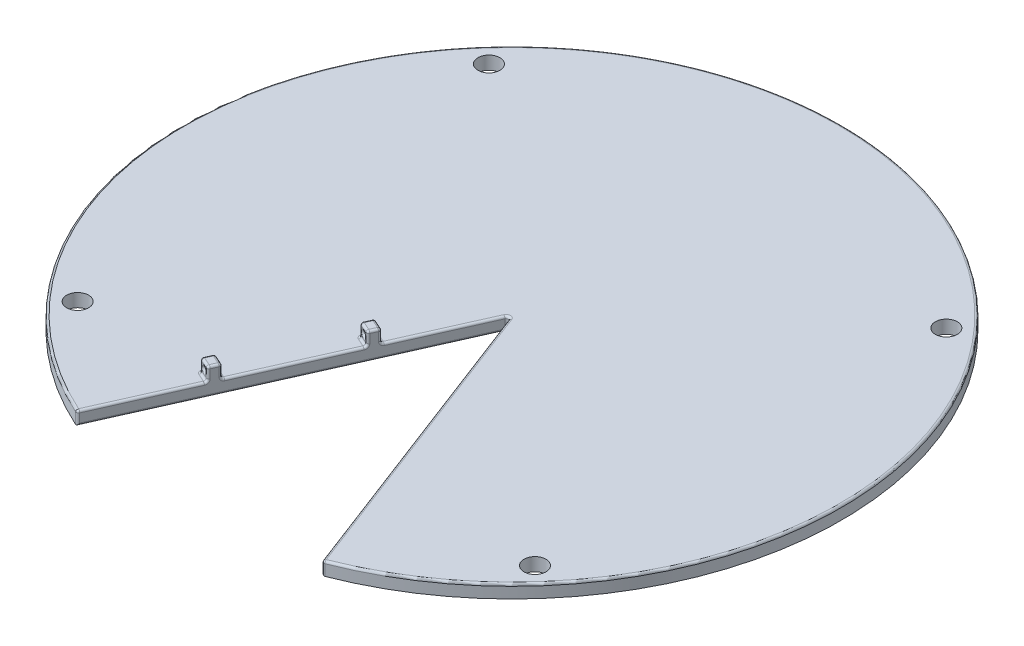
SolidWorks part; units mm, degrees
ref_plane "Front Plane" through (0, 0, 0) normal (0, 0, 1) x (1, 0, 0)
ref_plane "Top Plane" through (0, 0, 0) normal (0, 1, 0) x (1, 0, 0)
ref_plane "Right Plane" through (0, 0, 0) normal (1, 0, 0) x (0, 0, -1)
sketch "Sketch2" plane through (0, 0, 0) normal (0, 1, 0) x (1, 0, 0)
  circle A0 centre (0, 0) radius 75
extrude "Boss-Extrude1" add sketch "Sketch2" along normal blind 3
sketch "Sketch3" plane through (0, 3, 0) normal (0, 1, 0) x (1, 0, 0)
  line L0 (0, 0) -> (26.8315, -70.0362)
  line L1 (30.5503, 68.4958) -> (-26.8315, 70.0362)
  line L2 (-26.8315, 70.0362) -> (-68.4958, 30.5503)
  line L3 (-68.4958, 30.5503) -> (-70.0362, -26.8315)
  line L4 (-70.0362, -26.8315) -> (-30.5503, -68.4958)
  line L5 (-30.5503, -68.4958) -> (26.8315, -70.0362)
  line L6 (26.8315, -70.0362) -> (68.4958, -30.5503)
  line L7 (68.4958, -30.5503) -> (70.0362, 26.8315)
  line L8 (70.0362, 26.8315) -> (30.5503, 68.4958)
  line L9 (-30.5503, -68.4958) -> (0, 0)
  circle A1 centre (0, 0) radius 75 construction
  arc A4 (-30.5503, -68.4958) -> (26.8315, -70.0362) centre (0, 0) ccw
extrude "Cut-Extrude1" cut sketch "Sketch3" against normal blind 3 contours L5 A4 | L9 L5 L0 region at (-1.2396, 3, 46.1773) region at (-1.9209, 3, 71.5564)
sketch "Sketch4" plane through (0, 3, 0) normal (0, 1, 0) x (1, 0, 0)
  line L0 (-15.2752, -34.2479) -> (-21.3852, -47.9471)
  line L1 (-30.5503, -68.4958) -> (0, 0) construction
  line L2 (-21.3852, -47.9471) -> (-24.1251, -46.7251)
  line L3 (-24.1251, -46.7251) -> (-11.9049, -19.3267)
  line L4 (-11.9049, -19.3267) -> (-9.1651, -20.5487)
  line L5 (-9.1651, -20.5487) -> (-15.2752, -34.2479)
  dimension "D1" = 3
  dimension "D2" = 30
  dimension "D3" = 15
extrude "Boss-Extrude2" add sketch "Sketch4" along normal blind 3
sketch "Sketch5" plane through (0, 6, 0) normal (0, 1, 0) x (1, 0, 0)
  line L0 (-15.2752, -34.2479) -> (-10.1834, -22.8319)
  line L1 (-21.3852, -47.9471) -> (-9.1651, -20.5487) construction
  line L2 (-10.1834, -22.8319) -> (-12.9233, -21.6099)
  line L3 (-11.9049, -19.3267) -> (-24.1251, -46.7251) construction
  line L4 (-12.9233, -21.6099) -> (-23.1067, -44.4419)
  line L5 (-23.1067, -44.4419) -> (-20.3669, -45.6639)
  line L6 (-20.3669, -45.6639) -> (-15.2752, -34.2479)
  dimension "D1" = 12.5
  dimension "D2" = 12.5
extrude "Cut-Extrude2" cut sketch "Sketch5" against normal blind 3
sketch "Sketch6" plane through (-21.3852, 0, 47.9471) normal (-0.4073, 0, 0.9133) x (0.9133, 0, 0.4073)
  line L0 (-3, 6) -> (0, 6) construction
  circle A0 centre (-1.4723, 4.5) radius 0.5
  dimension "D1" = 1.5
extrude "Cut-Extrude3" cut sketch "Sketch6" against normal blind 30
fillet "Fillet3" radius 0.5 34 edges at (26.8315, 1.5, 70.0362) (13.4157, 0, 35.0181) (-11.9049, 4.5, 19.3267) (-23.1067, 4.5, 44.4419) (-9.1651, 4.5, 20.5487) (0, 1.5, 0) (-15.2752, 0, 34.2479) (-30.5503, 1.5, 68.4958) (-20.3669, 4.5, 45.6639) (-10.535, 6, 19.9377) (-9.6743, 6, 21.6903) (-12.4141, 6, 20.4683) (-10.1834, 4.5, 22.8319) (-12.9233, 4.5, 21.6099) (-11.5534, 6, 22.2209) (-11.9847, 4.5, 22.0286) (-24.1251, 4.5, 46.7251) (-21.3852, 4.5, 47.9471) (-22.2732, 4.5, 47.551) (-22.7552, 6, 47.3361) (-23.6159, 6, 45.5835) (-21.7368, 6, 45.0529) (-20.8761, 6, 46.8055) (-12.4141, 3, 20.4683) (-11.5534, 3, 22.2209) (-15.2752, 3, 34.2479) (-21.7368, 3, 45.0529) (-23.6159, 3, 45.5835) (-22.7552, 3, 47.3361) (-25.9678, 3, 58.2214) (2.0126, 3, -74.973) (13.4157, 3, 35.0181) (-4.5826, 3, 10.2744) (-10.535, 3, 19.9377)
sketch "Sketch8" plane through (0, 3, 0) normal (0, 1, 0) x (1, 0, 0)
  line L1 (-55.395, -49.8161) -> (55.395, -49.8161) construction
  line L2 (-55.395, -49.8161) -> (-55.395, 49.8161) construction
  line L3 (-55.395, 49.8161) -> (55.395, 49.8161) construction
  line L4 (55.395, -49.8161) -> (55.395, 49.8161) construction
  line L5 (-55.395, -49.8161) -> (55.395, 49.8161) construction
  line L6 (-55.395, 49.8161) -> (55.395, -49.8161) construction
  arc A0 (27.1189, -69.3889) -> (-30.8026, -67.834) centre (0, 0) ccw construction
  circle A1 centre (-52.049, 46.8071) radius 2.5
  circle A2 centre (52.049, 46.8071) radius 2.5
  circle A3 centre (-52.049, -46.8071) radius 2.5
  circle A4 centre (52.049, -46.8071) radius 2.5
  point P0 (0, 0)
  point P17 (0, 0)
  point P18 (0, 0)
  point P19 (0, 0)
  point P20 (0, 0)
  dimension "D1" = 70
  dimension "D2" = 70
  dimension "D3" = 70
  dimension "D4" = 70
extrude "Cut-Extrude4" cut sketch "Sketch8" against normal blind 10
